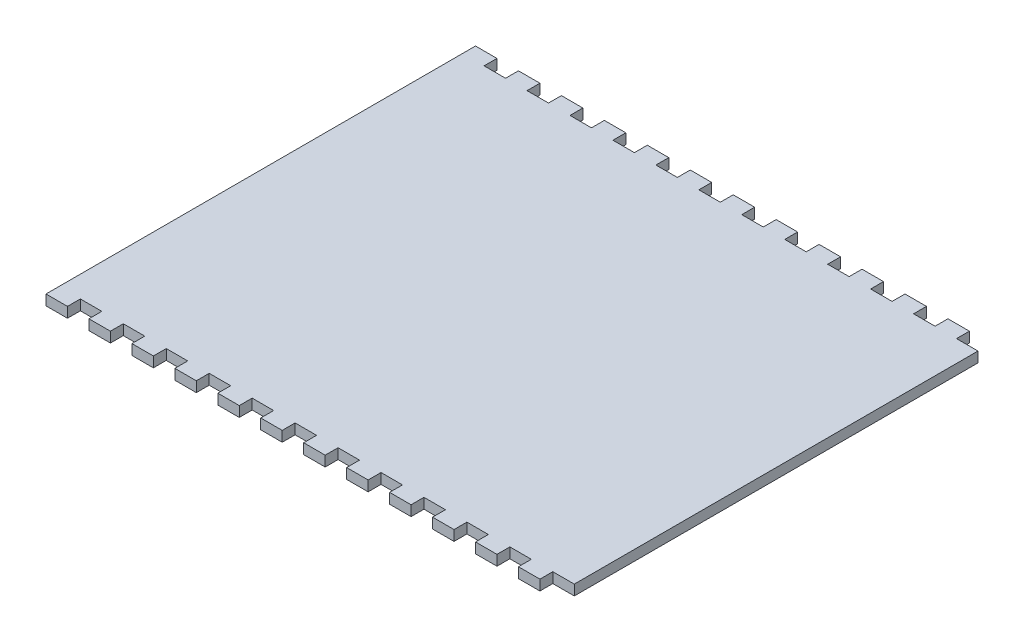
SolidWorks part; units mm, degrees
ref_plane "Front Plane" through (0, 0, 0) normal (0, 0, 1) x (1, 0, 0)
ref_plane "Top Plane" through (0, 0, 0) normal (0, 1, 0) x (1, 0, 0)
ref_plane "Right Plane" through (0, 0, 0) normal (1, 0, 0) x (0, 0, -1)
sketch "Sketch1" plane through (0, 0, 0) normal (0, 1, 0) x (1, 0, 0)
  line L1 (76.2, -63.5) -> (-76.2, -63.5)
  line L2 (76.2, -63.5) -> (76.2, 63.5)
  line L3 (76.2, 63.5) -> (-76.2, 63.5)
  line L4 (-76.2, -63.5) -> (-76.2, 63.5)
  line L5 (76.2, -63.5) -> (-76.2, 63.5) construction
  line L6 (76.2, 63.5) -> (-76.2, -63.5) construction
  point P0 (0, 0)
  dimension "D1" = 127
  dimension "D2" = 152.4
extrude "Boss-Extrude1" add sketch "Sketch1" along normal blind 3.048
sketch "Sketch2" plane through (0, 3.048, 0) normal (0, 1, 0) x (1, 0, 0)
  line L0 (-76.2, -63.5) -> (-69.85, -63.5)
  line L1 (-76.2, -63.5) -> (76.2, -63.5) construction
  line L2 (-69.85, -63.5) -> (-69.85, -59.69)
  line L3 (-69.85, -59.69) -> (-63.5, -59.69)
  line L4 (-63.5, -59.69) -> (-63.5, -63.5)
  line L5 (-63.5, -63.5) -> (-57.15, -63.5)
  line L6 (-57.15, -63.5) -> (-57.15, -59.69)
  line L7 (-57.15, -59.69) -> (-50.8, -59.69)
  line L8 (-50.8, -59.69) -> (-50.8, -63.5)
  line L9 (-50.8, -63.5) -> (-44.45, -63.5)
  line L10 (-44.45, -63.5) -> (-44.45, -59.69)
  line L11 (-44.45, -59.69) -> (-38.1, -59.69)
  line L12 (-38.1, -59.69) -> (-38.1, -63.5)
  line L13 (-38.1, -63.5) -> (-31.75, -63.5)
  line L14 (-31.75, -63.5) -> (-31.75, -59.69)
  line L15 (-31.75, -59.69) -> (-25.4, -59.69)
  line L16 (-25.4, -59.69) -> (-25.4, -63.5)
  line L17 (-25.4, -63.5) -> (-19.05, -63.5)
  line L18 (-19.05, -63.5) -> (-19.05, -59.69)
  line L19 (-19.05, -59.69) -> (-12.7, -59.69)
  line L20 (-12.7, -59.69) -> (-12.7, -63.5)
  line L21 (-12.7, -63.5) -> (-6.35, -63.5)
  line L22 (-6.35, -63.5) -> (-6.35, -59.69)
  line L23 (-6.35, -59.69) -> (0, -59.69)
  line L24 (0, -59.69) -> (0, -63.5)
  line L25 (0, -63.5) -> (6.35, -63.5)
  line L26 (6.35, -63.5) -> (6.35, -59.69)
  line L27 (6.35, -59.69) -> (12.7, -59.69)
  line L28 (12.7, -59.69) -> (12.7, -63.5)
  line L29 (12.7, -63.5) -> (19.05, -63.5)
  line L30 (19.05, -63.5) -> (19.05, -59.69)
  line L31 (19.05, -59.69) -> (25.4, -59.69)
  line L32 (25.4, -59.69) -> (25.4, -63.5)
  line L33 (25.4, -63.5) -> (31.75, -63.5)
  line L34 (31.75, -63.5) -> (31.75, -59.69)
  line L35 (31.75, -59.69) -> (38.1, -59.69)
  line L36 (38.1, -59.69) -> (38.1, -63.5)
  line L37 (38.1, -63.5) -> (44.45, -63.5)
  line L38 (44.45, -63.5) -> (44.45, -59.69)
  line L39 (44.45, -59.69) -> (50.8, -59.69)
  line L40 (50.8, -59.69) -> (50.8, -63.5)
  line L41 (50.8, -63.5) -> (57.15, -63.5)
  line L42 (57.15, -63.5) -> (57.15, -59.69)
  line L43 (57.15, -59.69) -> (63.5, -59.69)
  line L44 (63.5, -59.69) -> (63.5, -63.5)
  line L45 (63.5, -63.5) -> (69.85, -63.5)
  line L46 (69.85, -63.5) -> (69.85, -59.69)
  line L47 (69.85, -59.69) -> (76.2, -59.69)
  line L48 (76.2, -59.69) -> (76.2, -63.5)
  line L49 (-76.2, -63.5) -> (76.2, -63.5)
  line L50 (76.2, 0) -> (-76.2, 0)
  line L51 (76.2, -63.5) -> (76.2, 63.5) construction
  line L52 (-76.2, 63.5) -> (-76.2, -63.5) construction
  line L53 (-76.2, 63.5) -> (76.2, 63.5)
  line L54 (76.2, 59.69) -> (76.2, 63.5)
  line L55 (69.85, 59.69) -> (76.2, 59.69)
  line L56 (69.85, 63.5) -> (69.85, 59.69)
  line L57 (63.5, 63.5) -> (69.85, 63.5)
  line L58 (63.5, 59.69) -> (63.5, 63.5)
  line L59 (57.15, 59.69) -> (63.5, 59.69)
  line L60 (57.15, 63.5) -> (57.15, 59.69)
  line L61 (50.8, 63.5) -> (57.15, 63.5)
  line L62 (50.8, 59.69) -> (50.8, 63.5)
  line L63 (44.45, 59.69) -> (50.8, 59.69)
  line L64 (44.45, 63.5) -> (44.45, 59.69)
  line L65 (38.1, 63.5) -> (44.45, 63.5)
  line L66 (38.1, 59.69) -> (38.1, 63.5)
  line L67 (31.75, 59.69) -> (38.1, 59.69)
  line L68 (31.75, 63.5) -> (31.75, 59.69)
  line L69 (25.4, 63.5) -> (31.75, 63.5)
  line L70 (25.4, 59.69) -> (25.4, 63.5)
  line L71 (19.05, 59.69) -> (25.4, 59.69)
  line L72 (19.05, 63.5) -> (19.05, 59.69)
  line L73 (12.7, 63.5) -> (19.05, 63.5)
  line L74 (12.7, 59.69) -> (12.7, 63.5)
  line L75 (6.35, 59.69) -> (12.7, 59.69)
  line L76 (6.35, 63.5) -> (6.35, 59.69)
  line L77 (0, 63.5) -> (6.35, 63.5)
  line L78 (0, 59.69) -> (0, 63.5)
  line L79 (-6.35, 59.69) -> (0, 59.69)
  line L80 (-6.35, 63.5) -> (-6.35, 59.69)
  line L81 (-12.7, 63.5) -> (-6.35, 63.5)
  line L82 (-12.7, 59.69) -> (-12.7, 63.5)
  line L83 (-19.05, 59.69) -> (-12.7, 59.69)
  line L84 (-19.05, 63.5) -> (-19.05, 59.69)
  line L85 (-25.4, 63.5) -> (-19.05, 63.5)
  line L86 (-25.4, 59.69) -> (-25.4, 63.5)
  line L87 (-31.75, 59.69) -> (-25.4, 59.69)
  line L88 (-31.75, 63.5) -> (-31.75, 59.69)
  line L89 (-38.1, 63.5) -> (-31.75, 63.5)
  line L90 (-38.1, 59.69) -> (-38.1, 63.5)
  line L91 (-44.45, 59.69) -> (-38.1, 59.69)
  line L92 (-44.45, 63.5) -> (-44.45, 59.69)
  line L93 (-50.8, 63.5) -> (-44.45, 63.5)
  line L94 (-50.8, 59.69) -> (-50.8, 63.5)
  line L95 (-57.15, 59.69) -> (-50.8, 59.69)
  line L96 (-57.15, 63.5) -> (-57.15, 59.69)
  line L97 (-63.5, 63.5) -> (-57.15, 63.5)
  line L98 (-63.5, 59.69) -> (-63.5, 63.5)
  line L99 (-69.85, 59.69) -> (-63.5, 59.69)
  line L100 (-69.85, 63.5) -> (-69.85, 59.69)
  line L101 (-76.2, 63.5) -> (-69.85, 63.5)
  line M6 (-76.2, -63.5) -> (76.2, -63.5)
  line M7 (76.2, -63.5) -> (76.2, 63.5)
  line M8 (76.2, 63.5) -> (-76.2, 63.5)
  dimension "D1" = 6.35
  dimension "D2" = 6.35
  dimension "D3" = 3.81
  dimension "D4" = 12
extrude "Cut-Extrude1" cut sketch "Sketch2" against normal through all contours L4 L3 L2 M6 | L8 L7 L6 M6 | L12 L11 L10 M6 | L16 L15 L14 M6 | L20 L19 L18 M6 | L24 L23 L22 M6 | L28 L27 L26 M6 | L32 L31 L30 M6 | L40 L39 L38 M6 | L44 L43 L42 M6 | L36 L35 L34 M6 | L47 L46 M6 M7 | L100 L99 L98 M8 | L96 L95 L94 M8 | L92 L91 L90 M8 | L88 L87 L86 M8 | L84 L83 L82 M8 | L80 L79 L78 M8 | L76 L75 L74 M8 | L72 L71 L70 M8 | L68 L67 L66 M8 | L64 L63 L62 M8 | L60 L59 L58 M8 | L56 L55 M8 M7 region at (-66.675, 3.048, -61.595) region at (-53.975, 3.048, -61.595) region at (-41.275, 3.048, -61.595) region at (-28.575, 3.048, -61.595) region at (-15.875, 3.048, -61.595) region at (-3.175, 3.048, -61.595) region at (9.525, 3.048, -61.595) region at (22.225, 3.048, -61.595) region at (34.925, 3.048, -61.595) region at (47.625, 3.048, -61.595) region at (60.325, 3.048, -61.595) region at (73.025, 3.048, -61.595) region at (73.025, 3.048, 61.595) region at (60.325, 3.048, 61.595) region at (47.625, 3.048, 61.595) region at (34.925, 3.048, 61.595) region at (22.225, 3.048, 61.595) region at (9.525, 3.048, 61.595) region at (-3.175, 3.048, 61.595) region at (-15.875, 3.048, 61.595) region at (-28.575, 3.048, 61.595) region at (-41.275, 3.048, 61.595) region at (-53.975, 3.048, 61.595) region at (-66.675, 3.048, 61.595)
